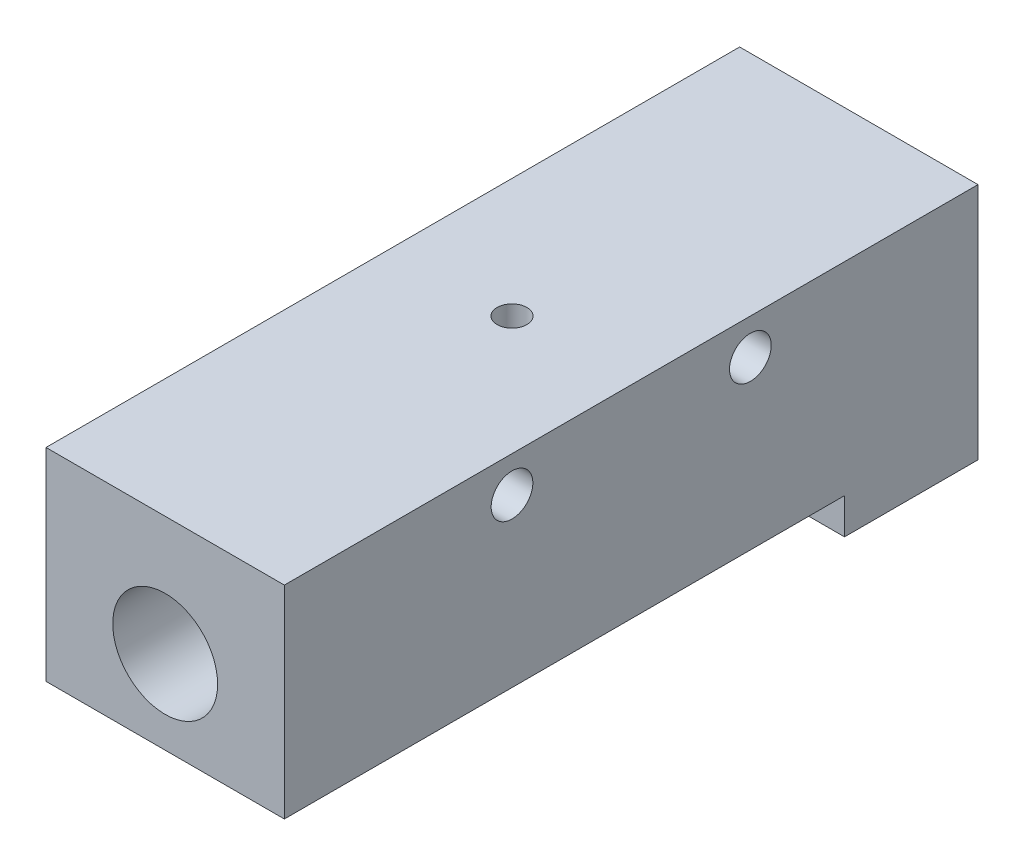
SolidWorks part; units mm, degrees
material "6063-T5"
ref_plane "Piano frontale" through (0, 0, 0) normal (0, 0, 1) x (1, 0, 0)
ref_plane "Piano superiore" through (0, 0, 0) normal (0, 1, 0) x (1, 0, 0)
ref_plane "Piano destro" through (0, 0, 0) normal (1, 0, 0) x (0, 0, -1)
sketch "Schizzo1" plane through (0, 0, 0) normal (0, 0, 1) x (1, 0, 0)
  line L1 (10, -10) -> (-10, -10)
  line L2 (10, -10) -> (10, 10)
  line L3 (10, 10) -> (-10, 10)
  line L4 (-10, -10) -> (-10, 10)
  line L5 (10, -10) -> (-10, 10) construction
  line L6 (10, 10) -> (-10, -10) construction
  point P0 (0, 0)
  dimension "D1" = 20
  dimension "D2" = 20
extrude "Estrusione-Estrusione1" add sketch "Schizzo1" against normal blind 58.2
sketch "Schizzo2" plane through (0, 0, -58.2) normal (0, 0, -1) x (-1, 0, 0)
  circle A0 centre (0, 0) radius 3
  dimension "D1" = 6
extrude "Taglio-Estrusione1" cut sketch "Schizzo2" against normal through all
sketch "Schizzo3" plane through (0, 0, -58.2) normal (0, 0, -1) x (-1, 0, 0)
  circle A0 centre (0, 0) radius 6
  dimension "D1" = 12
extrude "Taglio-Estrusione2" cut sketch "Schizzo3" against normal blind 13
sketch "Schizzo4" plane through (10, 0, 0) normal (1, 0, 0) x (0, 0, -1)
  line L0 (0, 7) -> (58.2, 7) construction
  line L1 (0, -10) -> (0, 10) construction
  line L2 (58.2, -10) -> (58.2, 10) construction
  line L3 (58.2, 10) -> (0, 10) construction
  line L4 (29.1, 10) -> (29.1, -10) construction
  line L5 (58.2, -10) -> (0, -10) construction
  circle A0 centre (19.1, 7) radius 1.75
  circle A1 centre (39.1, 7) radius 1.75
  dimension "D2" = 3.5
  dimension "D1" = 3
  dimension "D3" = 10
extrude "Taglio-Estrusione3" cut sketch "Schizzo4" against normal through all
hole_wizard "Foro filettato G1/8-1" positions "Schizzo8" profile "Schizzo7" tap size "G1/8" standard "BSI"
sketch "Schizzo8" plane through (0, 0, 0) normal (0, 0, 1) x (1, 0, 0)
  point P0 (0, 0)
sketch "Schizzo7" plane through (0, 0, 0) normal (1, 0, 0) x (0, -1, 0)
  line L0 (0, 0) -> (0, 12.6438)
  line L1 (0, 12.6438) -> (4.4, 10)
  line L2 (4.4, 10) -> (4.4, 0)
  line L5 (4.4, 0) -> (0, 0)
  line L10 (0, 12.6438) -> (-4.4, 10) construction
  line L11 (0, -6.35) -> (0, 107.95) construction
  dimension "Tap Drill Dia." = 8.8
  dimension "Tap Drill Depth" = 10
  dimension "Drill Angle" = 118
sketch "Schizzo10" plane through (10, 0, 0) normal (1, 0, 0) x (0, 0, -1)
  line L0 (0, -7) -> (47, -7)
  line L1 (0, -10) -> (0, 10) construction
  line L2 (47, -7) -> (47, -10)
  line L3 (58.2, -10) -> (0, -10) construction
  dimension "D1" = 47
  dimension "D2" = 3
extrude "Taglio-Estrusione5" cut sketch "Schizzo10" against normal through all and the other way through all flip side to cut
sketch "Schizzo11" plane through (0, 10, 0) normal (0, 1, 0) x (1, 0, 0)
  line L0 (0, 58.2) -> (0, 0) construction
  line L1 (10, 58.2) -> (-10, 58.2) construction
  line L2 (10, 29.1) -> (-10, 29.1) construction
  line L3 (10, 58.2) -> (10, 0) construction
  point P10 (0, 29.1)
  point P11 (0, 29.1)
  point P12 (0, 29.1)
hole_wizard "Foro filettato M3-1" positions "Schizzo3D1" profile "Schizzo12" tap size "M3" standard "DIN"
sketch3d "Schizzo3D1"
  point P0 (0, 10, -29.1)
sketch "Schizzo12" plane through (0, 10, -29.1) normal (1, 0, 0) x (0, 0, 1)
  line L0 (0, 0) -> (0, 5.7511)
  line L1 (0, 5.7511) -> (1.25, 5)
  line L2 (1.25, 5) -> (1.25, 0)
  line L5 (1.25, 0) -> (0, 0)
  line L10 (0, 5.7511) -> (-1.25, 5) construction
  line L11 (0, -6.35) -> (0, 107.95) construction
  dimension "Tap Drill Dia." = 2.5
  dimension "Tap Drill Depth" = 5
  dimension "Drill Angle" = 118
